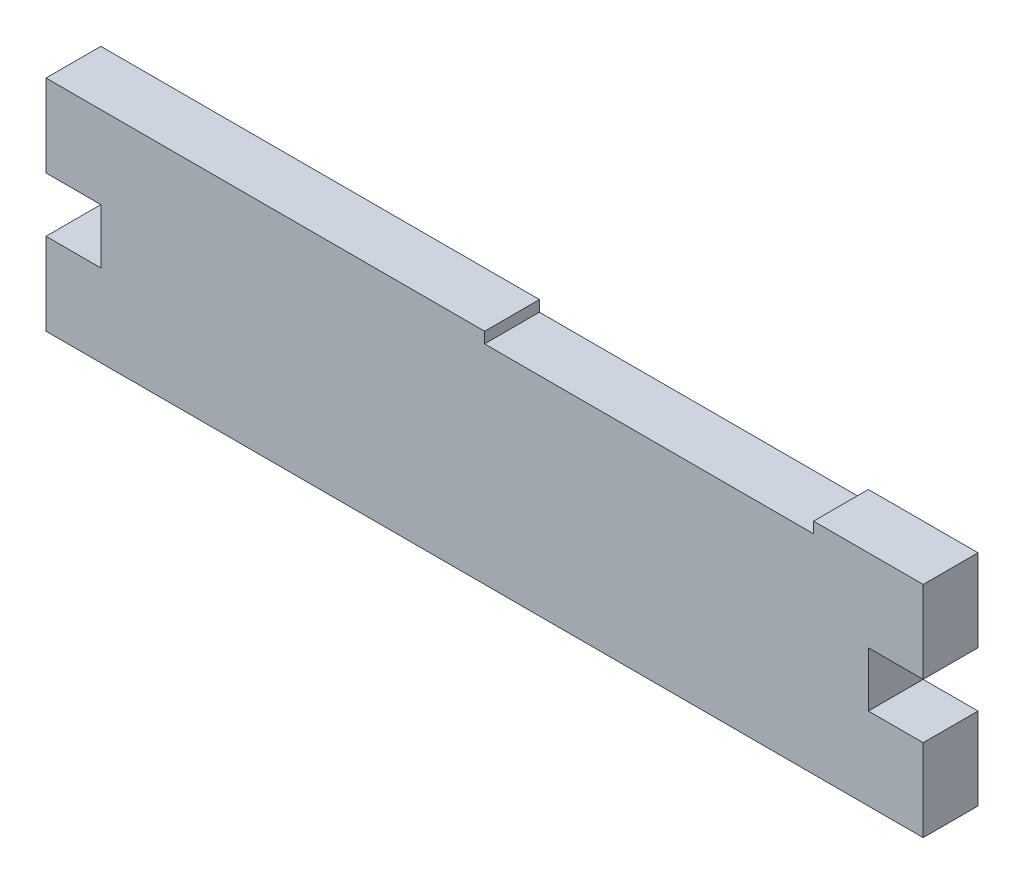
SolidWorks part; units mm, degrees
ref_plane "Plan de face" through (0, 0, 0) normal (0, 0, 1) x (1, 0, 0)
ref_plane "Plan de dessus" through (0, 0, 0) normal (0, 1, 0) x (1, 0, 0)
ref_plane "Plan de droite" through (0, 0, 0) normal (1, 0, 0) x (0, 0, -1)
sketch "Esquisse1" plane through (0, 0, 0) normal (0, 0, 1) x (1, 0, 0)
  line L0 (35, 0) -> (35, 20) construction
  line L1 (0, 0) -> (70, 0)
  line L2 (0, 7.5) -> (0, 12.5)
  line L3 (0, 20) -> (35, 20)
  line L4 (70, 7.5) -> (70, 12.5)
  line L5 (70, 0) -> (75, 0)
  line L6 (0, 20) -> (-5, 20)
  line L7 (65, 20) -> (70, 20)
  line L8 (0, 12.5) -> (-5, 12.5)
  line L9 (-5, 20) -> (-5, 12.5)
  line L10 (0, 0) -> (-5, 0)
  line L12 (0, 7.5) -> (-5, 7.5)
  line L13 (-5, 0) -> (-5, 7.5)
  line L14 (75, 0) -> (75, 7.5)
  line L15 (70, 7.5) -> (75, 7.5)
  line L16 (70, 12.5) -> (75, 12.5)
  line L17 (75, 20) -> (75, 12.5)
  line L18 (70, 20) -> (75, 20)
  line L19 (65, 20) -> (65, 19)
  line L20 (65, 19) -> (35, 19)
  line L21 (35, 20) -> (35, 19)
  dimension "D1" = 70
  dimension "D2" = 20
  dimension "D3" = 5
  dimension "D4" = 7.5
  dimension "D5" = 5
  dimension "D6" = 30
  dimension "D7" = 1
extrude "Boss.-Extru.1" add sketch "Esquisse1" along normal blind 5
